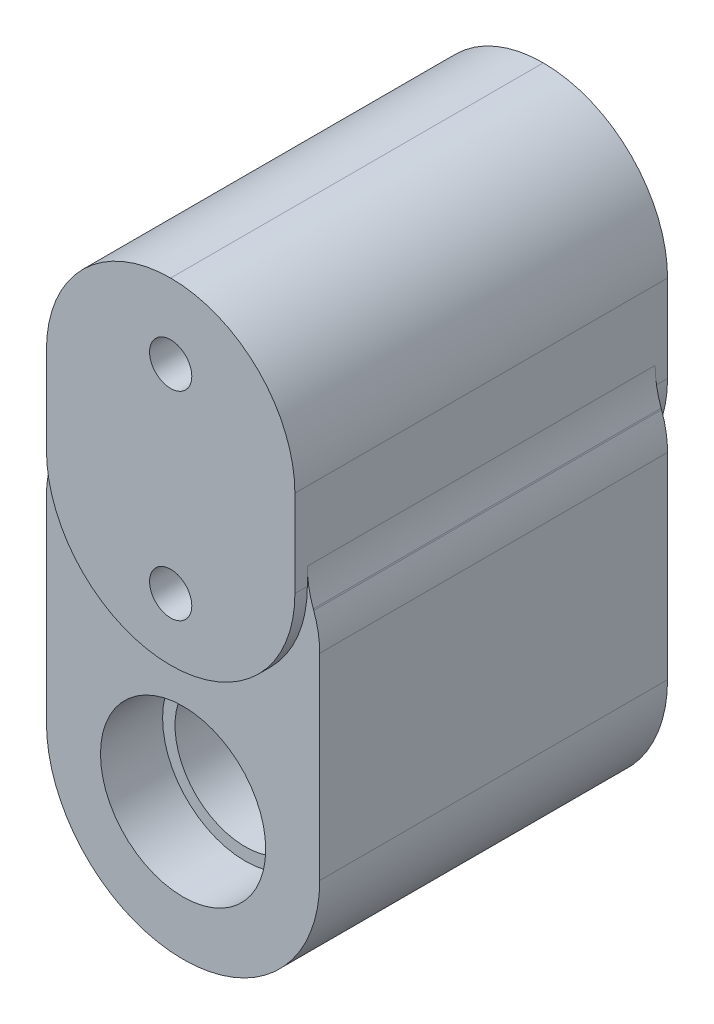
SolidWorks part; units mm, degrees
ref_plane "Спереди" through (0, 0, 0) normal (0, 0, 1) x (1, 0, 0)
ref_plane "Сверху" through (0, 0, 0) normal (0, 1, 0) x (1, 0, 0)
ref_plane "Справа" through (0, 0, 0) normal (1, 0, 0) x (0, 0, -1)
sketch "Эскиз1" plane through (0, 0, 0) normal (0, 0, 1) x (1, 0, 0)
  line L0 (0, 36) -> (0, -11) construction
  line L1 (-11, 37) -> (11, 37)
  line L2 (-11, 37) -> (-11, -11)
  line L3 (-11, -11) -> (11, -11)
  line L4 (11, 37) -> (11, -11)
  line L6 (-11, 0) -> (11, 0) construction
  dimension "D2" = 11
  dimension "D3" = 37
  dimension "D5" = 22
extrude "тело" add sketch "Эскиз1" along normal blind 14 and the other way blind 14
sketch "Эскиз2" plane through (0, 0, 14) normal (0, 0, 1) x (1, 0, 0)
  circle A0 centre (0, 0) radius 6.65
  dimension "D1" = 13.3
extrude "углубление для подшипника" cut sketch "Эскиз2" against normal blind 5
sketch "Эскиз4" plane through (0, 0, 9) normal (0, 0, 1) x (1, 0, 0)
  line L1 (0, 36) -> (0, -11) construction
  line L2 (-11, 0) -> (11, 0) construction
  circle A0 centre (0, 0) radius 5.65
  circle A1 centre (0, 0) radius 6.65 construction
  dimension "D1" = 1
extrude "сквозное отверстие" cut sketch "Эскиз4" against normal through all
mirror "Зеркальное отражение2" about plane through (0, 0, 0) normal (0, 0, 1) of "углубление для подшипника"
fillet "Скругление1" radius 11 2 edges at (11, -11, 0) (-11, -11, 0)
sketch "Эскиз5" plane through (0, 0, -14) normal (0, 0, -1) x (-1, 0, 0)
  line L0 (0, 37) -> (0, -11) construction
  line L1 (-11, 37) -> (11, 37) construction
  circle A0 centre (0, 31) radius 1.7
  circle A1 centre (0, 15) radius 1.7
  circle A2 centre (0, 0) radius 6.65 construction
  dimension "D1" = 3.4
  dimension "D2" = 16
  dimension "D3" = 15
extrude "отверстия для шурупов" cut sketch "Эскиз5" against normal through all
sketch "Эскиз9" plane through (0, 0, 14) normal (0, 0, 1) x (1, 0, 0)
  line L1 (-11, 10) -> (11, 10) construction
  line L2 (-10, 37) -> (10, 37)
  line L4 (-11, 37) -> (-11, 0) construction
  line L5 (11, 0) -> (11, 37) construction
  line L6 (-10, 20) -> (-10, 37)
  line L9 (10, 37) -> (10, 20)
  line L10 (11, 37) -> (-11, 37) construction
  arc A0 (-10, 20) -> (10, 20) centre (0, 20) ccw
  circle A1 centre (0, 15) radius 1.7
  circle A2 centre (0, 31) radius 1.7
  circle A3 centre (0, 31) radius 1.7 construction
  circle A5 centre (0, 15) radius 1.7 construction
  point P23 (0, 37)
  dimension "D1" = 10
  dimension "D2" = 5
  dimension "D3" = 20
extrude "выступы" add sketch "Эскиз9" along normal blind 1
mirror "Зеркальное отражение1" about plane through (0, 0, 0) normal (0, 0, 1) of "выступы"
sketch "Эскиз10" plane through (0, 0, 14) normal (0, 0, 1) x (1, 0, 0)
  line L0 (-10, 37) -> (-11, 37)
  line L1 (-11, 37) -> (-11, 17.2525)
  line L2 (-11, 37) -> (-11, 0) construction
  line L3 (0, 37) -> (0, 15) construction
  line L4 (-10, 37) -> (-10, 20)
  line L5 (-11, 17.2525) -> (-10, 20)
  line L6 (10, 37) -> (-10, 37) construction
  line L7 (11, 17.2525) -> (10, 20)
  line L8 (10, 37) -> (10, 20)
  line L9 (11, 37) -> (11, 17.2525)
  line L10 (10, 37) -> (11, 37)
  dimension "D1" = 20
extrude "Сглаживание перехода" cut sketch "Эскиз10" against normal up to next
fillet "Скругление2" radius 8 4 edges at (10, 20, 0) (11, 17.2525, 0) (-10, 20, 0) (-11, 17.2525, 0)
fillet "Скругление3" radius 10 2 edges at (-10, 37, 0) (10, 37, 0)
sketch "Эскиз11" plane through (0, 0, -15) normal (0, 0, -1) x (-1, 0, 0)
  line L1 (-21.9636, 39.8326) -> (21.5372, 39.8326)
  line L2 (-21.9636, 39.8326) -> (-21.9636, -13.9037)
  line L3 (-21.9636, -13.9037) -> (21.5372, -13.9037)
  line L4 (21.5372, 39.8326) -> (21.5372, -13.9037)
  dimension "D1" = 53.7363
  dimension "D2" = 43.5008
extrude "Сечение половиы (для раздельной печати)" [suppressed] cut sketch "Эскиз11" against normal up to surface (15 mm away) up to plane "Спереди"
